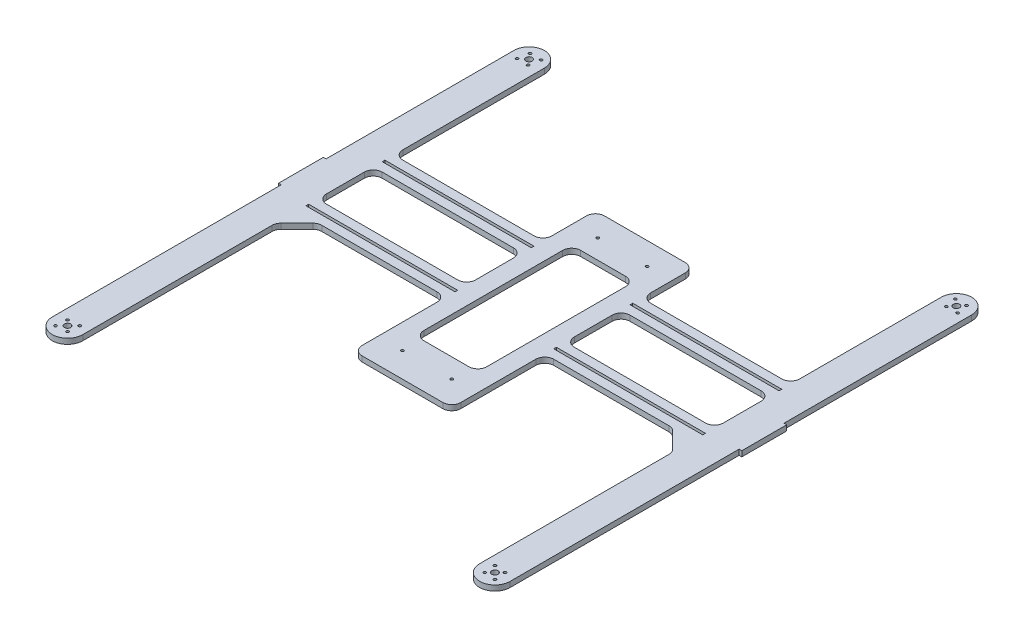
SolidWorks part; units mm, degrees
ref_plane "Front Plane" through (0, 0, 0) normal (0, 0, 1) x (1, 0, 0)
ref_plane "Top Plane" through (0, 0, 0) normal (0, 1, 0) x (1, 0, 0)
ref_plane "Right Plane" through (0, 0, 0) normal (1, 0, 0) x (0, 0, -1)
sketch "Sketch1" plane through (0, 0, 0) normal (0, 1, 0) x (1, 0, 0)
  line L1 (216, -40) -> (216, -255)
  line L4 (216, 78.5) -> (216, 81.5)
  line L5 (250, -255) -> (250, 0)
  line L6 (50, -120) -> (250, -120) construction
  line L7 (50, 150) -> (50, 91.5) construction
  line L8 (50, 150) -> (250, 120) construction
  line L10 (227.9078, 252.8902) -> (238.0922, 265.2304) construction
  line L11 (240.327, 253.0134) -> (225.673, 265.1073) construction
  line L12 (227.3431, -260.6569) -> (238.6569, -249.3431) construction
  line L13 (0, 25) -> (250, 25) construction
  line L14 (226.2825, -248.2825) -> (239.7175, -261.7175) construction
  line L18 (250, 0) -> (253, 0)
  line L19 (253, 0) -> (253, 50)
  line L20 (253, 50) -> (250, 50)
  line L21 (250, 50) -> (250, 259.0603)
  line L22 (50, 81.5) -> (50, 78.5) construction
  line L23 (50, 81.5) -> (50, 78.5)
  line L24 (50, -3.5) -> (50, -6.5) construction
  line L25 (50, -16.5) -> (50, -120) construction
  line L26 (50, 68.5) -> (50, 6.5)
  line L27 (-60, -5) -> (-226, -5) construction
  line L28 (216, 68.5) -> (216, 6.5)
  line L29 (-226, 68.5) -> (-226, 6.5)
  line L47 (-5, 150) -> (-5, -120) construction
  line L48 (-60, -120) -> (50, -120)
  line L53 (-60, 150) -> (50, 150)
  line L54 (50, 150) -> (50, 91.5)
  line L57 (250, -120) -> (250, -5) construction
  line L58 (50, -3.5) -> (50, -6.5)
  line L59 (216, -6.5) -> (50, -6.5)
  line L60 (50, 80) -> (216, 80) construction
  line L61 (250, 80) -> (250, 81.5) construction
  line L62 (216, 81.5) -> (50, 81.5)
  line L63 (216, -3.5) -> (50, -3.5)
  line L64 (250, 80) -> (250, 78.5) construction
  line L65 (216, 78.5) -> (50, 78.5)
  line L66 (-60, 80) -> (-226, 80) construction
  line L67 (50, 91.5) -> (216, 91.5)
  line L68 (-260, -120) -> (-260, -5) construction
  line L69 (50, 68.5) -> (216, 68.5)
  line L70 (50, -120) -> (50, -16.5)
  line L71 (-60, -16.5) -> (-60, -120) construction
  line L72 (50, -16.5) -> (192.5, -16.5)
  line L73 (-60, -3.5) -> (-60, -6.5) construction
  line L74 (50, 6.5) -> (216, 6.5)
  line L75 (192.5, -16.5) -> (216, -40)
  line L76 (50, -5) -> (216, -5) construction
  line L79 (216, -6.5) -> (216, -3.5)
  line L80 (216, 91.5) -> (216, 259.0603)
  line L81 (-60, 81.5) -> (-60, 78.5) construction
  line L82 (-236.2825, -248.2825) -> (-249.7175, -261.7175) construction
  line L83 (-10, 25) -> (-260, 25) construction
  line L84 (-237.3431, -260.6569) -> (-248.6569, -249.3431) construction
  line L85 (-250.327, 253.0134) -> (-235.673, 265.1073) construction
  line L86 (-237.9078, 252.8902) -> (-248.0922, 265.2304) construction
  line L87 (-60, 150) -> (-260, 120) construction
  line L88 (-60, 150) -> (-60, 91.5) construction
  line L89 (-60, -120) -> (-260, -120) construction
  line L90 (-226, 91.5) -> (-226, 259.0603)
  line L91 (-226, -6.5) -> (-226, -3.5)
  line L93 (-202.5, -16.5) -> (-226, -40)
  line L94 (-60, 6.5) -> (-226, 6.5)
  line L95 (-60, -16.5) -> (-202.5, -16.5)
  line L96 (-60, -120) -> (-60, -16.5)
  line L97 (-60, 68.5) -> (-226, 68.5)
  line L98 (-60, 91.5) -> (-226, 91.5)
  line L99 (-226, 78.5) -> (-60, 78.5)
  line L100 (-226, -3.5) -> (-60, -3.5)
  line L101 (-226, 81.5) -> (-60, 81.5)
  line L102 (-226, -6.5) -> (-60, -6.5)
  line L103 (-60, -3.5) -> (-60, -6.5)
  line L104 (-60, 150) -> (-60, 91.5)
  line L105 (-60, 68.5) -> (-60, 6.5)
  line L106 (-60, 81.5) -> (-60, 78.5)
  line L107 (-260, 50) -> (-260, 259.0603)
  line L108 (-263, 50) -> (-260, 50)
  line L109 (-263, 0) -> (-263, 50)
  line L110 (-260, 0) -> (-263, 0)
  line L111 (-260, -255) -> (-260, 0)
  line L112 (-226, 78.5) -> (-226, 81.5)
  line L113 (-226, -40) -> (-226, -255)
  line L121 (30, 103.5) -> (30, -71)
  line L122 (30, 103.5) -> (-40, 103.5)
  line L123 (-40, 103.5) -> (-40, -71)
  line L124 (-40, -71) -> (30, -71)
  arc A0 (216, -255) -> (250, -255) centre (233, -255) ccw
  arc A1 (216, 259.0603) -> (250, 259.0603) centre (233, 259.0603) cw
  circle A2 centre (233, -255) radius 135 construction
  circle A3 centre (233, 259.0603) radius 135 construction
  circle A4 centre (238.0922, 265.2304) radius 1.5
  circle A5 centre (225.673, 265.1073) radius 1.5
  circle A6 centre (227.9078, 252.8902) radius 1.5
  circle A7 centre (240.327, 253.0134) radius 1.5
  circle A8 centre (226.2825, -248.2825) radius 1.5
  circle A9 centre (238.6569, -249.3431) radius 1.5
  circle A10 centre (239.7175, -261.7175) radius 1.5
  circle A11 centre (227.3431, -260.6569) radius 1.5
  circle A33 centre (22.5, 125) radius 1.5
  circle A36 centre (-243, 259.0603) radius 135 construction
  circle A37 centre (-243, -255) radius 135 construction
  circle A39 centre (-32.5, 125) radius 1.5
  circle A40 centre (-237.3431, -260.6569) radius 1.5
  circle A41 centre (-249.7175, -261.7175) radius 1.5
  circle A42 centre (-248.6569, -249.3431) radius 1.5
  circle A43 centre (-236.2825, -248.2825) radius 1.5
  circle A44 centre (-250.327, 253.0134) radius 1.5
  circle A45 centre (-237.9078, 252.8902) radius 1.5
  circle A46 centre (-235.673, 265.1073) radius 1.5
  circle A47 centre (-248.0922, 265.2304) radius 1.5
  arc A48 (-226, 259.0603) -> (-260, 259.0603) centre (-243, 259.0603) ccw
  arc A49 (-226, -255) -> (-260, -255) centre (-243, -255) cw
  circle A50 centre (22.5, -92.5) radius 1.5
  circle A51 centre (-32.5, -92.5) radius 1.5
  circle A52 centre (-243, 259.0603) radius 3.5
  circle A53 centre (233, 259.0603) radius 3.5
  circle A54 centre (233, -255) radius 3.5
  circle A55 centre (-243, -255) radius 3.5
  point P12 (250, 120)
  point P13 (250, -120)
  point P15 (50, -120)
  point P134 (-60, -120)
  point P135 (-260, -120)
  point P136 (-260, 120)
  dimension "D1" = 17
  dimension "D3" = 270
  dimension "D4" = 270
  dimension "D12" = 3
  dimension "D13" = 3
  dimension "D14" = 3
  dimension "D15" = 3
  dimension "D20" = 3
  dimension "D21" = 3
  dimension "D22" = 3
  dimension "D23" = 3
  dimension "D24" = 7
  dimension "D7" = 7
  dimension "D8" = 7
  dimension "D11" = 7
  dimension "D5" = 240
  dimension "D6" = 200
  dimension "D9" = 16
  dimension "D10" = 19
  dimension "D16" = 270
  dimension "D17" = 45
  dimension "D18" = 16
  dimension "D19" = 19
extrude "Boss-Extrude1" add sketch "Sketch1" along normal blind 6 contours L1 A0 L5 L8 L4 L7 A11 A10 A9 A8 | L7 | A1 L4 L8 L5 A7 A6 A5 A4 region at (209.5727, 0, 22.9273)
fillet "Скругление1" radius 10 26 edges at (216, 3, -6.5) (216, 3, -68.5) (216, 3, -91.5) (-226, 3, -6.5) (-226, 3, -68.5) (-226, 3, -91.5) (-226, 3, 40) (-202.5, 3, 16.5) (216, 3, 40) (192.5, 3, 16.5) (-40, 3, 71) (30, 3, 71) (30, 3, -103.5) (-40, 3, -103.5) (-60, 3, -150) (50, 3, -150) (-60, 3, 120) (50, 3, 120) (50, 3, -68.5) (50, 3, -91.5) (50, 3, -6.5) (50, 3, 16.5) (-60, 3, -91.5) (-60, 3, 16.5) (-60, 3, -6.5) (-60, 3, -68.5)
